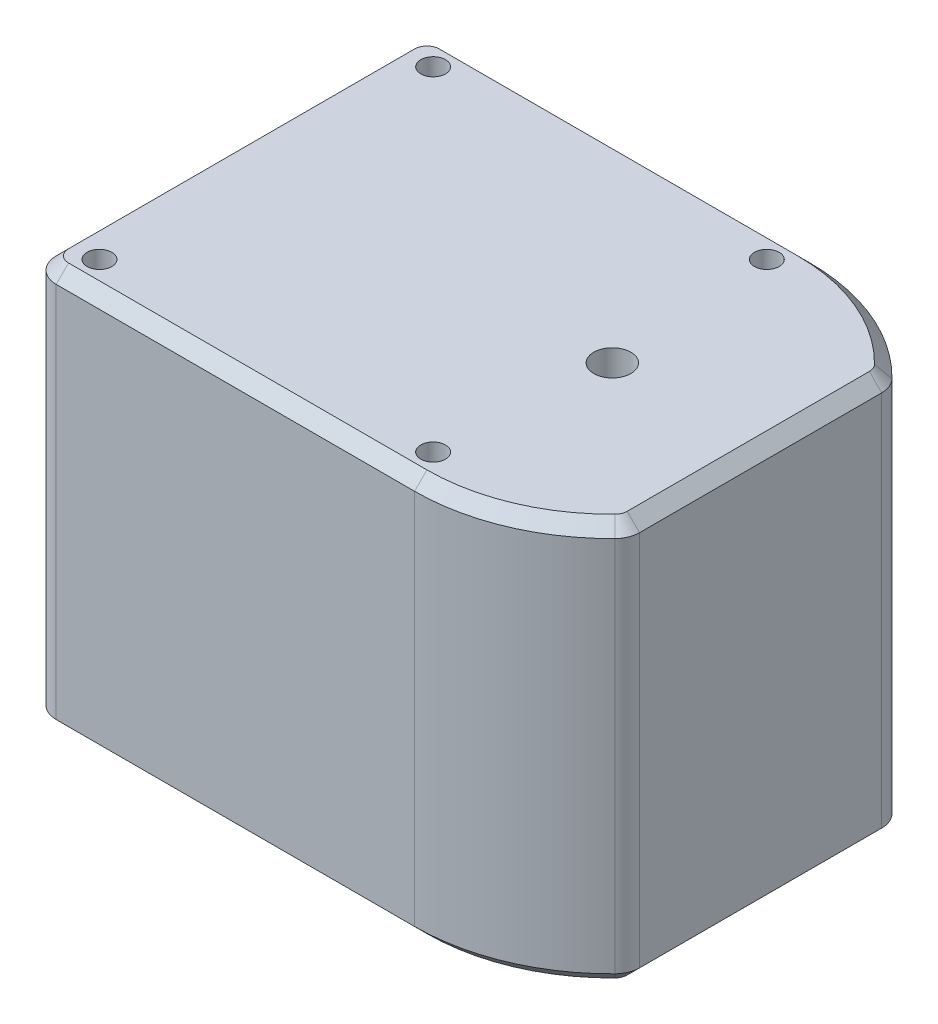
SolidWorks part; units mm, degrees
ref_plane "Front" through (0, 0, 0) normal (0, 0, 1) x (1, 0, 0)
ref_plane "Top" through (0, 0, 0) normal (0, 1, 0) x (1, 0, 0)
ref_plane "Right" through (0, 0, 0) normal (1, 0, 0) x (0, 0, -1)
sketch "Эскиз2" plane through (0, 0, 0) normal (0, 1, 0) x (1, 0, 0)
  line L0 (0, 0) -> (-42.3953, 0) construction
  line L1 (-31, -16) -> (12, -16)
  line L2 (-31, -16) -> (-31, 16)
  line L3 (-31, 16) -> (12, 16)
  line L4 (12, -16) -> (12, 16)
  line L5 (-31, -16) -> (12, 16) construction
  line L6 (-31, 16) -> (12, -16) construction
  line L7 (0, 0) -> (0, 25.0609) construction
  circle A0 centre (0, 0) radius 16
  circle A1 centre (0, 0) radius 1.5
  point P0 (-9.5, 0)
  dimension "D1" = 43
  dimension "D2" = 32
  dimension "D3" = 9.5
extrude "Бобышка-Вытянуть1" add sketch "Эскиз2" along normal blind 16.25 and the other way blind 16.25 contours A0 L4 | A0 L3 L2 L1 region at (-21.4373, 0, 0) region at (-15.5748, 0, 0)
sketch "Эскиз3" plane through (0, 0, 0) normal (0, 1, 0) x (1, 0, 0)
  line L0 (0, 0) -> (-31, 0) construction
  line L1 (-31, -16) -> (-31, 16) construction
  line L3 (-1, -13.5) -> (-28, -13.5) construction
  line L4 (-1, -13.5) -> (-1, 13.5) construction
  line L5 (-1, 13.5) -> (-28, 13.5) construction
  line L6 (-28, -13.5) -> (-28, 13.5) construction
  line L7 (-1, -13.5) -> (-28, 13.5) construction
  line L8 (-1, 13.5) -> (-28, -13.5) construction
  circle A0 centre (-28, 13.5) radius 1
  circle A1 centre (-1, 13.5) radius 1
  circle A2 centre (-1, -13.5) radius 1
  circle A3 centre (-28, -13.5) radius 1
  point P5 (-14.5, 0)
  dimension "D1" = 27
  dimension "D2" = 27
  dimension "D3" = 14.5
extrude "Вырез-Вытянуть1" cut sketch "Эскиз3" against normal through all both and the other way through all
fillet "Скругление1" radius 2 4 edges at (12, 0, -10.583) (12, 0, 10.583) (-31, 0, -16) (-31, 0, 16)
chamfer "Фаска1" distance 1 angle 45 20 edges at (6.1983, -16.25, -14.7506) (-14.5, -16.25, -16) (11.8516, -16.25, -10.5539) (-30.4142, -16.25, -15.4142) (12, -16.25, 0) (-31, -16.25, 0) (11.8516, -16.25, 10.5539) (-30.4142, -16.25, 15.4142) (6.1983, -16.25, 14.7506) (-14.5, -16.25, 16) (6.1983, 16.25, -14.7506) (-14.5, 16.25, -16) (11.8516, 16.25, -10.5539) (-30.4142, 16.25, -15.4142) (12, 16.25, 0) (-31, 16.25, 0) (11.8516, 16.25, 10.5539) (-30.4142, 16.25, 15.4142) (6.1983, 16.25, 14.7506) (-14.5, 16.25, 16)
sketch "Эскиз4" plane through (0, 0, 0) normal (0, 0, 1) x (1, 0, 0)
  line L0 (-31, -15.25) -> (-31, 15.25) construction
  line L1 (-12, -11.15) -> (-3.5, -11.15)
  line L2 (-12, -11.15) -> (-12, -15.15)
  line L3 (-12, -15.15) -> (-3.5, -15.15)
  line L4 (-3.5, -11.15) -> (-3.5, -15.15)
  line L5 (-12, -11.15) -> (-3.5, -15.15) construction
  line L6 (-12, -15.15) -> (-3.5, -11.15) construction
  line L7 (0, 0) -> (-31, 0)
  line L8 (-31, 0) -> (-31, -18.3497)
  line L9 (0, 0) -> (0, -16.25)
  line L10 (0, -16.25) -> (-11.0384, -16.25)
  line L11 (0, -16.25) -> (-29, -16.25) construction
  point P0 (-7.75, -13.15)
  dimension "D1" = 8.5
  dimension "D2" = 4
  dimension "D3" = 19
  dimension "D4" = 5.1
extrude "Вырез-Вытянуть2" cut sketch "Эскиз4" against normal through all contours L4 L1 L2 L3 region at (-7.75, -13.15, 0)
